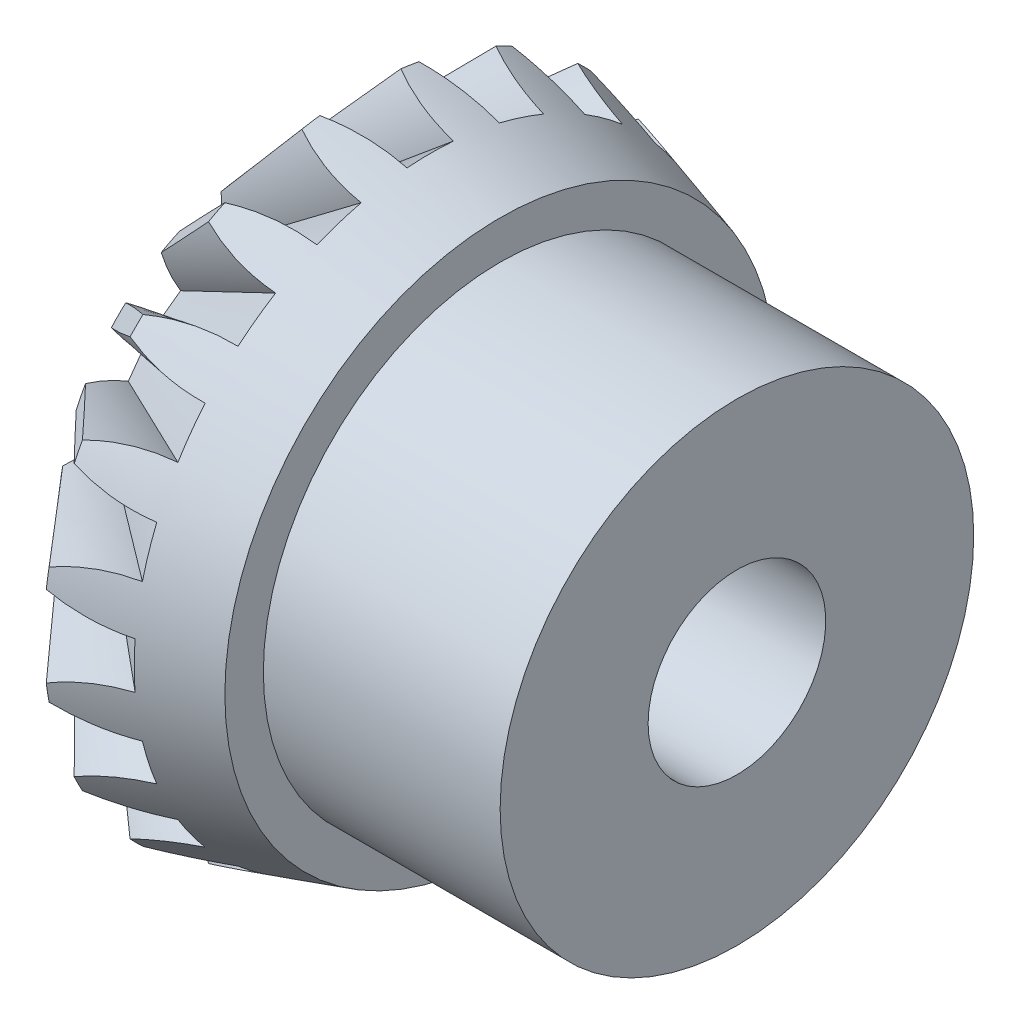
SolidWorks part; units mm, degrees
ref_plane "Front" through (0, 0, 0) normal (0, 0, 1) x (1, 0, 0)
ref_plane "Top" through (0, 0, 0) normal (0, 1, 0) x (1, 0, 0)
ref_plane "Right" through (0, 0, 0) normal (1, 0, 0) x (0, 0, -1)
sketch "Sketch1" plane through (0, 0, 0) normal (0, 0, 1) x (1, 0, 0)
  line L0 (0, 0) -> (8, 0) construction
  line L1 (0, 1.5) -> (8, 1.5)
  line L2 (8, 1.5) -> (8, 4)
  line L3 (8, 4) -> (4, 4)
  line L4 (4, 4) -> (4, 4.65)
  line L5 (4, 4.65) -> (1.6397, 5.35)
  line L6 (1.6397, 5.35) -> (0, 3.4628)
  line L7 (0, 3.4628) -> (0, 1.5)
  line L8 (2.8199, 5) -> (0, 1.7546) construction
  dimension "D1" = 49.013
  dimension "Overall Length" = 8
  dimension "OD" = 10.7
  dimension "For Shaft" = 3
  dimension "Face Width" = 2.5
  dimension "Hub Dia" = 8
  dimension "Hub Width" = 4
  dimension "PD" = 10
revolve "Revolve1" add sketch "Sketch1" angle 360 about L0
sketch "Sketch2" plane through (0, 0, 0) normal (-1, 0, 0) x (0, 0, 1)
  circle A0 centre (0, 0) radius 5
  dimension "Pitch Dia" = 10
sketch "Sketch3" plane through (0, 0, 0) normal (-1, 0, 0) x (0, 0, 1)
  line L0 (-10, 0) -> (10, 0) construction
  point P2 (0, 0)
  dimension "teeth" = 20
sketch "Sketch5" plane through (0, 0, 0) normal (-1, 0, 0) x (0, 0, 1)
  line L0 (0, 0) -> (0, 5.35) construction
  line L1 (0, 0) -> (0.4198, 5.3335) construction
  line L2 (0, 0) -> (-0.4198, 5.3335) construction
  line L4 (-10, 0) -> (10, 0) construction
  line L5 (-0.2099, 2.6668) -> (0.2099, 2.6668)
  line L6 (0, 0) -> (-1.6532, 5.0882) construction
  line L7 (0, 0) -> (1.6532, 5.0882) construction
  circle A0 centre (0, 0) radius 5.35 construction
  arc A1 (-0.2099, 2.6668) -> (-1.6532, 5.0882) centre (-3.3814, 2.4172) ccw
  arc A2 (0.2099, 2.6668) -> (1.6532, 5.0882) centre (3.3814, 2.4172) cw
  arc A3 (-1.6532, 5.0882) -> (1.6532, 5.0882) centre (0, 0) cw
  point P10 (0, 0)
  dimension "D1" = 9
  dimension "D2" = 36
ref_plane "Plane1" through (2.8199, 0, 0) normal (1, 0, 0) x (0, 0, -1)
sketch "Sketch6" plane through (2.8199, 0, 0) normal (1, 0, 0) x (0, 0, -1)
  line L0 (0, 0) -> (0, 8.025) construction
  line L1 (0, 0) -> (0.4198, 5.3335) construction
  line L2 (0, 0) -> (-0.4198, 5.3335) construction
  line L3 (0, 0) -> (2.6075, 8.025) construction
  line L4 (0, 0) -> (-2.6075, 8.025) construction
  line L5 (2.6075, 8.025) -> (-2.6075, 8.025) construction
  line L6 (0, 5.35) -> (0, 0) construction
  line L7 (-2.6075, 8.025) -> (2.6075, 8.025)
  circle A0 centre (0, 0) radius 5.35 construction
  arc A1 (-0.3923, 4.9846) -> (-2.6075, 8.025) centre (-3.9732, 4.7028) ccw
  arc A2 (0.3923, 4.9846) -> (2.6075, 8.025) centre (3.9732, 4.7028) cw
  circle A3 centre (0, 0) radius 5 construction
  arc A4 (0.3923, 4.9846) -> (-0.3923, 4.9846) centre (0, 0) ccw
  dimension "D1" = 9
  dimension "D2" = 36
  dimension "D3" = 8.025
  dimension "D4" = 5.35
loft "Cut-Loft1" cut profiles "Sketch6", "Sketch5" connector at (2.8199, 8.025, -2.6075) connector at (0, 5.0882, -1.6532)
pattern_circular "CirPattern1" count 20 over 360 about axis through (0, 0, 0) along (-1, 0, 0) of "Cut-Loft1"
sketch "Sketch7" plane through (0, 0, 0) normal (-1, 0, 0) x (0, 0, 1)
  circle A0 centre (0, 0) radius 5
sketch "Sketch8"
  dimension "D1" = 11
sketch_block_instance "Block1-1"
sketch_block "Block1"
ref_axis "Axis1" through (8, 0, 0) along (-1, 0, 0)
ref_plane "Plane3" through (0, 0, 0) normal (-1, 0, 0) x (0, 0, 1)
equation "\"D1@Sketch5\"=(360deg/20)/2"
equation "\"D2@Sketch5\"=(360deg/20)/.5"
equation "\"D1@Sketch6\"=(360deg/\"teeth@Sketch5\")/2"
equation "\"D2@Sketch6\"=(360deg/\"teeth@Sketch5\")/.5"
equation "\"D3@Sketch6\"=\"D4@Sketch6\"*1.5"
equation "\"D1@Sketch8\"=\"Mounting Distance@Sketch8\""
